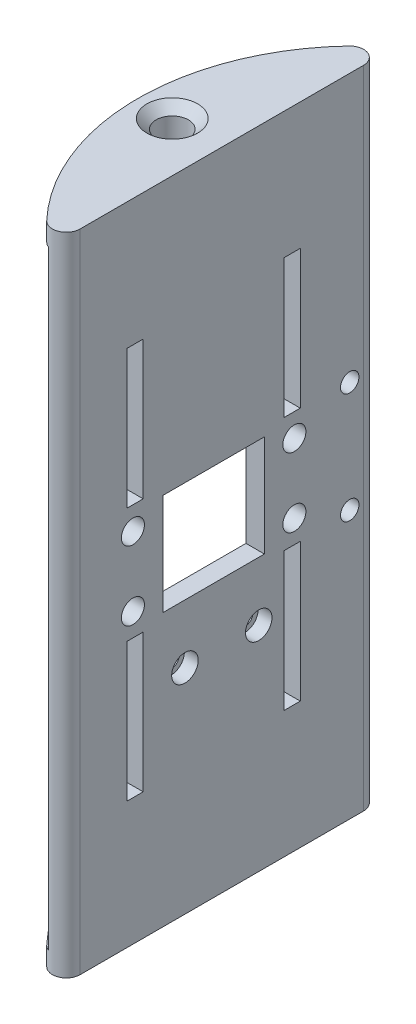
SolidWorks part; units mm, degrees
ref_plane "Front Plane" through (0, 0, 0) normal (1, 0, 0) x (0, 1, 0)
ref_plane "Top Plane" through (0, 0, 0) normal (0, 0, 1) x (0, 1, 0)
ref_plane "Right Plane" through (0, 0, 0) normal (0, 1, 0) x (-1, 0, 0)
sketch "Sketch1" plane through (0, 0, 0) normal (0, 0, 1) x (0, 1, 0)
  line L0 (-8.186, 0) -> (-8.186, -21.2483)
  line L1 (-8.186, -21.2483) -> (131.814, -21.2483)
  line L2 (131.814, -21.2483) -> (131.814, 0)
  line L3 (131.814, 0) -> (123.814, 0)
  line L4 (123.814, 0) -> (123.814, -17.2483)
  line L5 (123.814, -17.2483) -> (-0.186, -17.2483)
  line L6 (-0.186, -17.2483) -> (-0.186, 0)
  line L7 (-0.186, 0) -> (-8.186, 0)
  line L8 (-12.186, -30.6238) -> (-12.186, -16.002) construction
  line L10 (135.814, -16.002) -> (135.814, 53.9758) construction
  dimension "D1" = 4
  dimension "D2" = 8
  dimension "D3" = 4
  dimension "D4" = 4
  dimension "D5" = 140
extrude "Boss-Extrude1" add sketch "Sketch1" along normal blind 75
sketch "Sketch2" plane through (0, -8.186, 0) normal (0, -1, 0) x (1, 0, 0)
  line L0 (21.2483, 37.5) -> (0, 37.5) construction
  line L1 (21.2483, 75) -> (21.2483, 0) construction
  line L2 (0, 75) -> (0, 0) construction
  circle A0 centre (10.5, 37.5) radius 3.5
  dimension "D1" = 7
  dimension "D2" = 7
extrude "Cut-Extrude1" cut sketch "Sketch2" against normal offset from surface (7 mm away) 1 up to face at (8.6242, -0.186, 37.5)
sketch "Sketch3" plane through (0, 131.814, 0) normal (0, 1, 0) x (-1, 0, 0)
  circle A0 centre (-10.5, 37.5) radius 3.5 construction
  circle A1 centre (-10.5, 37.5) radius 3.5
extrude "Cut-Extrude2" cut sketch "Sketch3" against normal offset from surface (7 mm away) 1 up to face at (8.6242, 123.814, 37.5)
sketch "Sketch6" plane through (0, -0.186, 0) normal (0, 1, 0) x (-1, 0, 0)
  line L4 (-17.2483, 0) -> (0, 0)
  line L5 (0, 0) -> (0, 75)
  line L6 (0, 75) -> (-17.2483, 75)
  line L7 (-17.2483, 75) -> (-17.2483, 0)
  line L8 (-17.2483, 0) -> (0, 0)
  line L9 (0, 0) -> (0, 75)
  line L10 (0, 75) -> (-17.2483, 75)
  line L11 (-17.2483, 75) -> (-17.2483, 0)
  circle A1 centre (-10.5, 37.5) radius 4
  circle A3 centre (-10.5, 37.5) radius 3.5 construction
  dimension "D2" = 8
  dimension "D1" = 0
extrude "Cut-Extrude3" cut sketch "Sketch6" against normal blind 4
sketch "Sketch7" plane through (0, 123.814, 0) normal (0, -1, 0) x (1, 0, 0)
  line L4 (0, 0) -> (17.2483, 0)
  line L5 (17.2483, 0) -> (17.2483, 75)
  line L6 (17.2483, 75) -> (0, 75)
  line L7 (0, 75) -> (0, 0)
  line L8 (0, 0) -> (17.2483, 0)
  line L9 (17.2483, 0) -> (17.2483, 75)
  line L10 (17.2483, 75) -> (0, 75)
  line L11 (0, 75) -> (0, 0)
  circle A2 centre (10.5, 37.5) radius 4
  circle A3 centre (10.5, 37.5) radius 3.5 construction
  dimension "D1" = 8
  dimension "D2" = 0
extrude "Cut-Extrude4" cut sketch "Sketch7" against normal blind 4
fillet "Fillet6" radius 4 2 edges at (10.5, 127.814, 33.5) (10.5, -4.186, 41.5)
chamfer "Chamfer1" distance 2 angle 45 2 edges at (10.5, -8.186, 34) (10.5, 131.814, 41)
sketch "Sketch10" plane through (0, -8.186, 0) normal (0, -1, 0) x (1, 0, 0)
  line L6 (21.2483, 75) -> (0, 75)
  line L7 (0, 75) -> (0, 0) construction
  line L8 (0, 75) -> (21.2483, 75) construction
  line L9 (0, 75) -> (0, 0)
  line L10 (0, 0) -> (21.2483, 0)
  arc A1 (21.2483, 75) -> (21.2483, 0) centre (50.6551, 37.5) ccw
  circle A4 centre (10.5, 37.5) radius 5.5 construction
  dimension "D1" = 2
extrude "Cut-Extrude9" cut sketch "Sketch10" against normal through all
fillet "Fillet11" radius 3 2 edges at (21.2483, 61.814, 75) (21.2483, 61.814, 0)
sketch "Sketch14" plane through (21.2483, 0, 0) normal (1, 0, 0) x (0, 1, 0)
  line L2 (131.814, 5.8571) -> (131.814, 74.4281) construction
  line L3 (-8.186, 74.4281) -> (-8.186, 5.8571) construction
  line L4 (-8.186, 40.1426) -> (131.814, 40.1426) construction
  line L5 (61.814, 8.6855) -> (61.814, 71.5997) construction
  line L8 (104.314, 58.0522) -> (74.314, 58.0522)
  line L9 (19.314, 54.5522) -> (49.314, 54.5522)
  line L10 (19.314, 54.5522) -> (19.314, 58.0522)
  line L11 (19.314, 58.0522) -> (49.314, 58.0522)
  line L12 (49.314, 54.5522) -> (49.314, 58.0522)
  line L13 (19.314, 54.5522) -> (49.314, 58.0522) construction
  line L14 (19.314, 58.0522) -> (49.314, 54.5522) construction
  line L15 (74.314, 54.5522) -> (74.314, 58.0522)
  line L16 (104.314, 54.5522) -> (74.314, 54.5522)
  line L17 (104.314, 54.5522) -> (104.314, 58.0522)
  line L18 (54.314, 56.7774) -> (54.314, 21.7774) construction
  line L19 (54.314, 39.2774) -> (68.2197, 39.2774) construction
  line L20 (104.314, 24.0026) -> (104.314, 20.5026)
  line L21 (104.314, 24.0026) -> (74.314, 24.0026)
  line L22 (74.314, 24.0026) -> (74.314, 20.5026)
  line L23 (104.314, 20.5026) -> (74.314, 20.5026)
  line L24 (19.314, 20.5026) -> (49.314, 20.5026)
  line L25 (49.314, 24.0026) -> (49.314, 20.5026)
  line L26 (19.314, 24.0026) -> (49.314, 24.0026)
  line L27 (19.314, 24.0026) -> (19.314, 20.5026)
  line L28 (-8.186, 68.2226) -> (-8.186, 6.7774) construction
  line L29 (131.814, 68.2226) -> (131.814, 6.7774) construction
  line L30 (-8.186, 6.7774) -> (131.814, 6.7774) construction
  circle A0 centre (54.314, 21.7774) radius 2.5
  circle A1 centre (54.314, 56.7774) radius 2.5
  circle A2 centre (69.314, 56.7774) radius 2.5
  circle A3 centre (69.314, 21.7774) radius 2.5
  circle A4 centre (49.814, 9.7774) radius 2
  circle A5 centre (73.814, 9.7774) radius 2
  point P24 (34.314, 56.3022)
  point P45 (61.814, 6.7774)
  dimension "D3" = 2.5
  dimension "D4" = 5
  dimension "D8" = 4
  dimension "D1" = 3.5
  dimension "D2" = 30
  dimension "D5" = 15
  dimension "D6" = 35
  dimension "D7" = 15
  dimension "D9" = 24
  dimension "D10" = 3
extrude "Cut-Extrude13" cut sketch "Sketch14" against normal up to next
sketch "Sketch16" plane through (21.2483, 0, 0) normal (1, 0, 0) x (0, 1, 0)
  line L0 (54.314, 21.7774) -> (69.314, 56.7774) construction
  line L1 (54.314, 56.7774) -> (69.314, 21.7774) construction
  line L3 (50.814, 28.2774) -> (72.814, 28.2774)
  line L4 (50.814, 28.2774) -> (50.814, 50.2774)
  line L5 (50.814, 50.2774) -> (72.814, 50.2774)
  line L6 (72.814, 28.2774) -> (72.814, 50.2774)
  line L7 (50.814, 28.2774) -> (72.814, 50.2774) construction
  line L8 (50.814, 50.2774) -> (72.814, 28.2774) construction
  point P8 (61.814, 39.2774)
  dimension "D1" = 22
extrude "Cut-Extrude14" cut sketch "Sketch16" against normal up to next
sketch "Sketch17" plane through (17.2483, 0, 0) normal (-1, 0, 0) x (0, -1, 0)
  line L0 (-127.814, 43.0156) -> (-3.6818, 43.0156) construction
  line L7 (-41.814, 50) -> (-39.814, 50)
  line L8 (-41.814, 50) -> (-41.814, 42.5)
  line L9 (-41.814, 42.5) -> (-39.814, 42.5)
  line L10 (-39.814, 50) -> (-39.814, 42.5)
  line L11 (-28.814, 50) -> (-26.814, 50)
  line L12 (-28.814, 50) -> (-28.814, 42.5)
  line L13 (-28.814, 42.5) -> (-26.814, 42.5)
  line L14 (-26.814, 50) -> (-26.814, 42.5)
  line L15 (-49.314, 58.0522) -> (-49.314, 54.5522) construction
  line L16 (-26.814, 25) -> (-26.814, 43.5312)
  line L17 (-28.814, 43.5312) -> (-26.814, 43.5312)
  line L18 (-28.814, 25) -> (-28.814, 43.5312)
  line L19 (-28.814, 25) -> (-26.814, 25)
  line L20 (-39.814, 13.9688) -> (-39.814, 43.5312)
  line L21 (-41.814, 43.5312) -> (-39.814, 43.5312)
  line L22 (-41.814, 13.9688) -> (-41.814, 43.5312)
  line L23 (-41.814, 13.9688) -> (-39.814, 13.9688)
  line L24 (-127.814, 40.5312) -> (-127.814, 45.5) construction
  line L25 (-41.814, 46.25) -> (-39.814, 46.25) construction
  line L26 (-39.814, 28.75) -> (-41.814, 28.75) construction
  dimension "D1" = 11
  dimension "D2" = 2
  dimension "D3" = 7.5
  dimension "D4" = 17.5
  dimension "D5" = 7.5
ref_plane "Plane1" through (0, 41.814, 0) normal (0, -1, 0) x (1, 0, 0)
sketch "Sketch19" plane through (0, 41.814, 0) normal (0, -1, 0) x (1, 0, 0)
  line L0 (17.2483, 54.5522) -> (17.2483, 58.0522) construction
  line L2 (17.2483, 54.5522) -> (17.2483, 58.0522) construction
  line L3 (17.2483, 24.0026) -> (17.2483, 20.5026) construction
  line L4 (17.2483, 26.0026) -> (17.2483, 42.0026)
  line L5 (17.2483, 3.949) -> (17.2483, 33.2034) construction
  line L6 (3, 37.5) -> (31.5641, 37.5) construction
  line L7 (17.2483, 26.0026) -> (10.5, 26.0026)
  line L8 (10.5, 26.0026) -> (10.5, 42.0026)
  line L9 (10.5, 48.9974) -> (17.2483, 48.9974)
  line L12 (10.5, 42.0026) -> (10.5, 48.9974)
  line L13 (17.2483, 42.0026) -> (17.2483, 48.9974)
  line L14 (17.2483, 24.0026) -> (17.2483, 20.5026) construction
  line L15 (10.5, 29.5) -> (17.2483, 29.5) construction
  line L16 (10.5, 45.5) -> (17.2483, 45.5) construction
  arc A0 (3.0965, 40.5312) -> (3.0965, 34.4688) centre (50.6551, 37.5) ccw construction
  circle A1 centre (10.5, 37.5) radius 4 construction
  arc A2 (14.5, 37.5) -> (6.5, 37.5) centre (10.5, 37.5) ccw construction
  point P19 (0, 0)
  point P21 (0, 0)
  point P22 (0, 0)
  dimension "D1" = 2
  dimension "D2" = 8
  dimension "D3" = 8
extrude "Boss-Extrude3" add sketch "Sketch19" along normal blind 7.5
sketch "Sketch20" plane through (10.5, 0, 0) normal (-1, 0, 0) x (0, -1, 0)
  line L0 (-34.314, 37.5) -> (-41.814, 37.5) construction
  line L1 (-34.314, 26.0026) -> (-34.314, 48.9974) construction
  line L4 (-41.814, 26.0026) -> (-41.814, 48.9974) construction
  circle A0 centre (-38.064, 45.5) radius 1.75
  circle A1 centre (-38.064, 29.5) radius 1.75
  dimension "D1" = 3.5
  dimension "D2" = 16
extrude "Cut-Extrude16" cut sketch "Sketch20" against normal through all
sketch "Sketch21" plane through (21.2483, 0, 0) normal (1, 0, 0) x (0, 1, 0)
  circle A0 centre (38.064, 45.5) radius 2.875
  circle A1 centre (38.064, 29.5) radius 2.875
  dimension "D1" = 5.75
extrude "Cut-Extrude17" cut sketch "Sketch21" against normal blind 3
